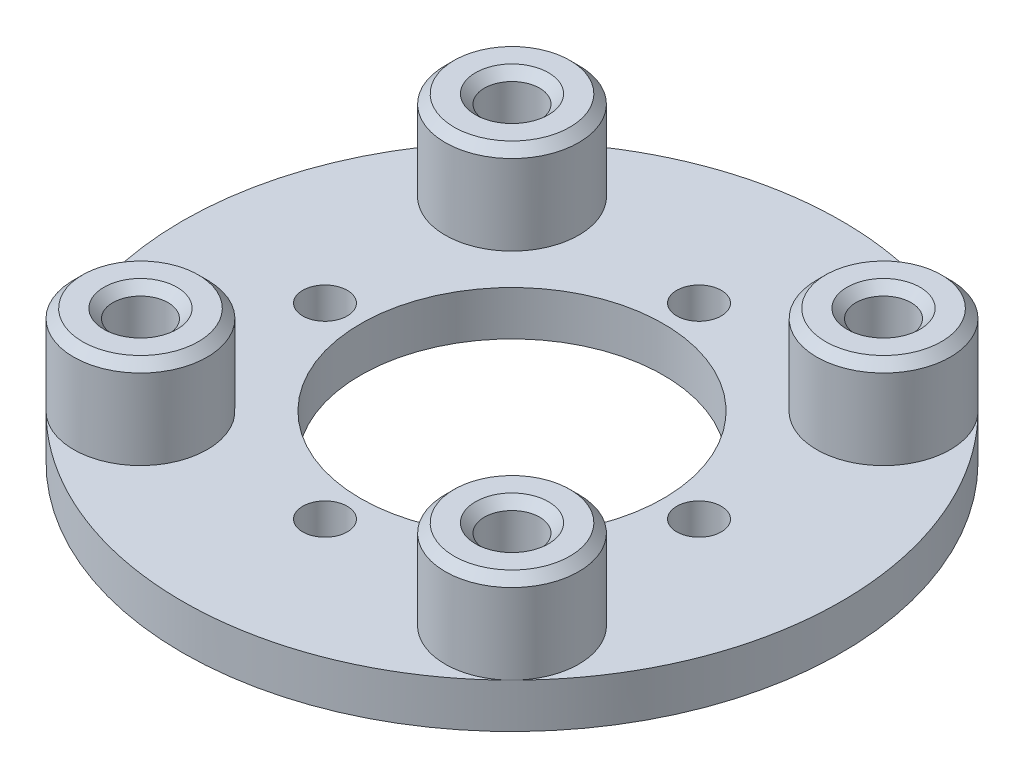
SolidWorks part; units mm, degrees
ref_plane "Front" through (0, 0, 0) normal (0, 0, 1) x (1, 0, 0)
ref_plane "Top" through (0, 0, 0) normal (0, 1, 0) x (1, 0, 0)
ref_plane "Right" through (0, 0, 0) normal (1, 0, 0) x (0, 0, -1)
sketch "草图1" plane through (0, 0, 0) normal (0, 1, 0) x (1, 0, 0)
  circle A0 centre (0, 0) radius 37
  circle A1 centre (21, 0) radius 2.5
  circle A2 centre (0, -21) radius 2.5
  circle A3 centre (-21, 0) radius 2.5
  circle A4 centre (0, 21) radius 2.5
  circle A5 centre (0, 0) radius 17
  point P14 (0, 0)
  dimension "D1" = 74
  dimension "D3" = 5
  dimension "D4" = 34
  dimension "D2" = 21
extrude "凸台-拉伸1" add sketch "草图1" along normal blind 5
sketch "草图2" plane through (0, 0, 0) normal (0, -1, 0) x (1, 0, 0)
  line L0 (0, 0) -> (34.2419, 34.2419) construction
  circle A0 centre (20.8597, 20.8597) radius 3.1
  circle A1 centre (20.8597, -20.8597) radius 3.1
  circle A2 centre (-20.8597, -20.8597) radius 3.1
  circle A3 centre (-20.8597, 20.8597) radius 3.1
  point P14 (0, 0)
  dimension "D1" = 6.2
  dimension "D2" = 29.5
ref_plane "基准面1" through (0, 50, 0) normal (0, 1, 0) x (1, 0, 0)
sketch "草图4" plane through (0, 5, 0) normal (0, 1, 0) x (1, 0, 0)
  circle A0 centre (20.8597, -20.8597) radius 7.5
  circle A2 centre (-20.8597, -20.8597) radius 7.5
  circle A4 centre (-20.8597, 20.8597) radius 7.5
  circle A6 centre (20.8597, 20.8597) radius 7.5
  point P16 (0, 0)
  dimension "D1" = 4
sketch "草图3" plane through (0, 50, 0) normal (0, 1, 0) x (1, 0, 0)
  line L0 (-48.3593, 0) -> (48.1025, 0) construction
  line L1 (-24.5, -24.5) -> (24.5, -24.5)
  line L2 (-24.5, -24.5) -> (-24.5, 24.5)
  line L3 (-24.5, 24.5) -> (24.5, 24.5)
  line L4 (24.5, -24.5) -> (24.5, 24.5)
  line L5 (-24.5, -24.5) -> (24.5, 24.5) construction
  line L6 (-24.5, 24.5) -> (24.5, -24.5) construction
  line L7 (0, 44.9496) -> (0, -39.3078) construction
  circle A0 centre (15.5, 15.5) radius 1.75
  circle A1 centre (0, 0) radius 11.1
  circle A2 centre (15.5, -15.5) radius 1.75
  circle A3 centre (-15.5, -15.5) radius 1.75
  circle A4 centre (-15.5, 15.5) radius 1.75
  point P0 (0, 0)
  point P23 (0, 0)
  dimension "D3" = 3.5
  dimension "D5" = 22.2
  dimension "D1" = 49
  dimension "D2" = 49
  dimension "D4" = 15.5
extrude "凸台-拉伸9" add sketch "草图4" along normal blind 10
extrude "切除-拉伸1" cut sketch "草图2" against normal up to next
chamfer "倒角1" distance 1 angle 45 12 edges at (20.8597, 0, -23.9597) (-20.8597, 0, -23.9597) (-20.8597, 0, 17.7597) (20.8597, 0, 17.7597) (20.8597, 15, -17.7597) (-20.8597, 15, -17.7597) (-20.8597, 15, 23.9597) (20.8597, 15, 23.9597) (20.8597, 15, 28.3597) (20.8597, 15, -13.3597) (-20.8597, 15, -13.3597) (-20.8597, 15, 28.3597)
